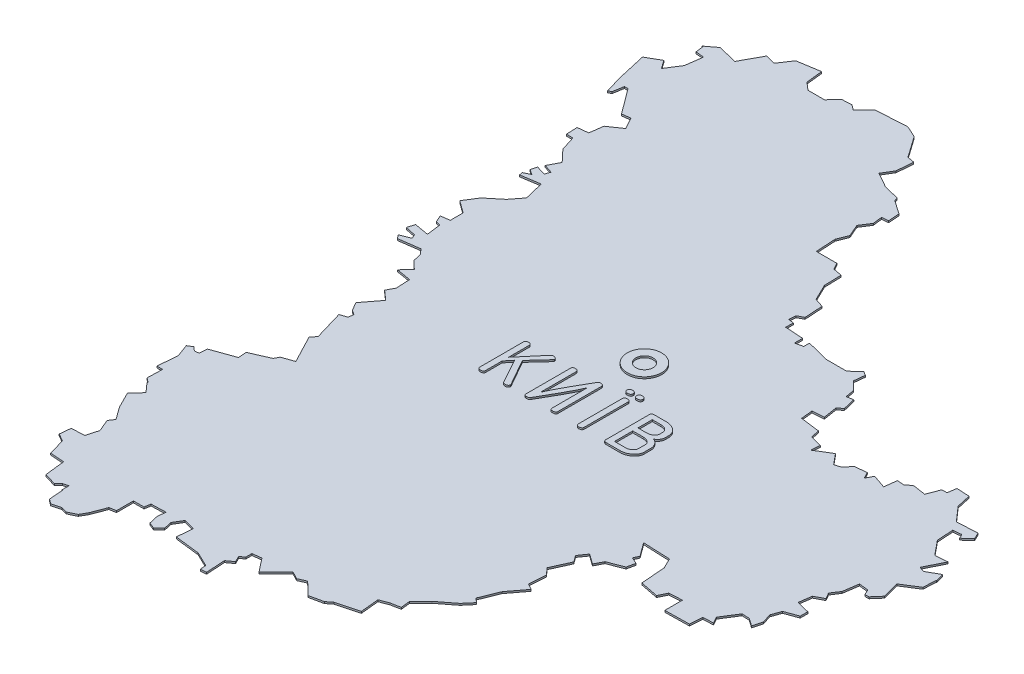
SolidWorks part; units mm, degrees
ref_plane "Спереди" through (0, 0, 0) normal (0, 0, 1) x (1, 0, 0)
ref_plane "Сверху" through (0, 0, 0) normal (0, 1, 0) x (1, 0, 0)
ref_plane "Справа" through (0, 0, 0) normal (1, 0, 0) x (0, 0, -1)
sketch "Эскиз1" plane through (0, 0, 0) normal (0, 1, 0) x (1, 0, 0)
  line B0 (1334.8284, 6150.008) -> (1323.1393, 6150.008)
  line B1 (1323.1393, 6150.008) -> (1316.0248, 6165.596)
  line B2 (1316.0248, 6165.596) -> (1288.7579, 6168.8421)
  line B3 (1288.7579, 6168.8421) -> (1282.253, 6124.7274)
  line B4 (1282.253, 6124.7274) -> (1266.7031, 6100.7193)
  line B5 (1266.7031, 6100.7193) -> (1277.0434, 6083.1806)
  line B6 (1277.0434, 6083.1806) -> (1251.0999, 6069.5408)
  line B7 (1251.0999, 6069.5408) -> (1245.8903, 6032.5584)
  line B8 (1245.8903, 6032.5584) -> (1283.5509, 6023.4805)
  line B9 (1283.5509, 6023.4805) -> (1283.5509, 6001.4155)
  line B10 (1283.5509, 6001.4155) -> (1245.8903, 5987.7858)
  line B11 (1245.8903, 5987.7858) -> (1236.185, 5960.5418)
  line B12 (1236.185, 5960.5418) -> (1244.6457, 5933.2749)
  line B13 (1244.6457, 5933.2749) -> (1237.4804, 5906.0258)
  line B14 (1237.4804, 5906.0258) -> (1215.4484, 5921.5833)
  line B15 (1215.4484, 5921.5833) -> (1193.3403, 5922.8914)
  line B16 (1193.3403, 5922.8914) -> (1164.1455, 5876.8285)
  line B17 (1164.1455, 5876.8285) -> (1174.5366, 5857.9944)
  line B18 (1174.5366, 5857.9944) -> (1145.3139, 5856.7066)
  line B19 (1145.3139, 5856.7066) -> (1142.0881, 5820.3567)
  line B20 (1142.0881, 5820.3567) -> (1072.0299, 5819.0587)
  line B21 (1072.0299, 5819.0587) -> (1072.0299, 5870.3362)
  line B22 (1072.0299, 5870.3362) -> (1034.3972, 5868.3906)
  line B23 (1034.3972, 5868.3906) -> (1022.6573, 5844.3724)
  line B24 (1022.6573, 5844.3724) -> (969.4723, 5854.7432)
  line B25 (969.4723, 5854.7432) -> (964.2881, 5924.8294)
  line B26 (964.2881, 5924.8294) -> (949.3479, 5955.3399)
  line B27 (949.3479, 5955.3399) -> (870.8288, 5958.6038)
  line B28 (870.8288, 5958.6038) -> (899.3886, 5919.6554)
  line B29 (899.3886, 5919.6554) -> (892.8837, 5904.0751)
  line B30 (892.8837, 5904.0751) -> (911.7381, 5895.6423)
  line B31 (911.7381, 5895.6423) -> (906.5285, 5871.6139)
  line B32 (906.5285, 5871.6139) -> (862.4164, 5854.7432)
  line B33 (862.4164, 5854.7432) -> (850.0923, 5830.7427)
  line B34 (850.0923, 5830.7427) -> (820.8696, 5851.5098)
  line B35 (820.8696, 5851.5098) -> (804.0218, 5827.489)
  line B36 (804.0218, 5827.489) -> (817.6184, 5808.693)
  line B37 (817.6184, 5808.693) -> (793.6052, 5755.4597)
  line B38 (793.6052, 5755.4597) -> (811.088, 5735.353)
  line B39 (811.088, 5735.353) -> (807.2755, 5687.3064)
  line B40 (807.2755, 5687.3064) -> (824.7837, 5677.5731)
  line B41 (824.7837, 5677.5731) -> (788.3957, 5629.5722)
  line B42 (788.3957, 5629.5722) -> (766.3383, 5575.0663)
  line B43 (766.3383, 5575.0663) -> (778.6878, 5564.6726)
  line B44 (778.6878, 5564.6726) -> (756.6304, 5538.7291)
  line B45 (756.6304, 5538.7291) -> (710.5879, 5503.0268)
  line B46 (710.5879, 5503.0268) -> (678.1114, 5470.5758)
  line B47 (678.1114, 5470.5758) -> (681.3398, 5443.3368)
  line B48 (681.3398, 5443.3368) -> (654.0983, 5438.1273)
  line B49 (654.0983, 5438.1273) -> (628.1293, 5428.394)
  line B50 (628.1293, 5428.394) -> (633.3388, 5375.209)
  line B51 (633.3388, 5375.209) -> (570.3697, 5358.3129)
  line B52 (570.3697, 5358.3129) -> (554.8198, 5345.9863)
  line B53 (554.8198, 5345.9863) -> (515.8638, 5337.5255)
  line B54 (515.8638, 5337.5255) -> (478.8916, 5373.2532)
  line B55 (478.8916, 5373.2532) -> (456.8088, 5363.4945)
  line B56 (456.8088, 5363.4945) -> (434.0911, 5375.209)
  line B57 (434.0911, 5375.209) -> (384.7948, 5325.8872)
  line B58 (384.7948, 5325.8872) -> (354.3021, 5364.8178)
  line B59 (354.3021, 5364.8178) -> (328.3331, 5361.5387)
  line B60 (328.3331, 5361.5387) -> (328.3331, 5344.6909)
  line B61 (328.3331, 5344.6909) -> (316.644, 5334.2997)
  line B62 (316.644, 5334.2997) -> (325.0794, 5317.4265)
  line B63 (325.0794, 5317.4265) -> (306.2757, 5303.8045)
  line B64 (306.2757, 5303.8045) -> (309.5041, 5248.6382)
  line B65 (309.5041, 5248.6382) -> (292.6309, 5247.3428)
  line B66 (292.6309, 5247.3428) -> (291.3355, 5264.2414)
  line B67 (291.3355, 5264.2414) -> (248.4907, 5285.0009)
  line B68 (248.4907, 5285.0009) -> (176.4767, 5293.4387)
  line B69 (176.4767, 5293.4387) -> (180.3654, 5339.5067)
  line B70 (180.3654, 5339.5067) -> (147.9169, 5347.9446)
  line B71 (147.9169, 5347.9446) -> (132.3391, 5321.9731)
  line B72 (132.3391, 5321.9731) -> (137.5486, 5298.6229)
  line B73 (137.5486, 5298.6229) -> (120.6754, 5283.0197)
  line B74 (120.6754, 5283.0197) -> (103.1418, 5290.185)
  line B75 (103.1418, 5290.185) -> (96.6622, 5318.7219)
  line B76 (96.6622, 5318.7219) -> (99.8906, 5340.7793)
  line B77 (99.8906, 5340.7793) -> (57.0713, 5339.5067)
  line B78 (57.0713, 5339.5067) -> (53.8201, 5321.9731)
  line B79 (53.8201, 5321.9731) -> (23.3274, 5321.9731)
  line B80 (23.3274, 5321.9731) -> (23.3274, 5272.6514)
  line B81 (23.3274, 5272.6514) -> (4.4983, 5269.4002)
  line B82 (4.4983, 5269.4002) -> (-11.0541, 5228.5392)
  line B83 (-11.0541, 5228.5392) -> (-22.7432, 5207.7518)
  line B84 (-22.7432, 5207.7518) -> (-46.7817, 5196.0882)
  line B85 (-46.7817, 5196.0882) -> (-63.6041, 5201.2723)
  line B86 (-63.6041, 5201.2723) -> (-89.5731, 5194.1324)
  line B87 (-89.5731, 5194.1324) -> (-103.218, 5204.526)
  line B88 (-103.218, 5204.526) -> (-106.4717, 5245.387)
  line B89 (-106.4717, 5245.387) -> (-108.4021, 5245.387)
  line B90 (-108.4021, 5245.387) -> (-108.4021, 5266.1464)
  line B91 (-108.4021, 5266.1464) -> (-123.9799, 5262.2577)
  line B92 (-123.9799, 5262.2577) -> (-135.669, 5250.5966)
  line B93 (-135.669, 5250.5966) -> (-170.0759, 5260.9877)
  line B94 (-170.0759, 5260.9877) -> (-174.5971, 5298.6229)
  line B95 (-174.5971, 5298.6229) -> (-176.53, 5318.7219)
  line B96 (-176.53, 5318.7219) -> (-217.4392, 5321.9731)
  line B97 (-217.4392, 5321.9731) -> (-231.0613, 5369.9994)
  line B98 (-231.0613, 5369.9994) -> (-253.1161, 5382.326)
  line B99 (-253.1161, 5382.326) -> (-249.8903, 5414.1141)
  line B100 (-249.8903, 5414.1141) -> (-212.2322, 5416.0699)
  line B101 (-212.2322, 5416.0699) -> (-202.499, 5450.4514)
  line B102 (-202.499, 5450.4514) -> (-217.4392, 5486.1536)
  line B103 (-217.4392, 5486.1536) -> (-207.0481, 5501.7314)
  line B104 (-207.0481, 5501.7314) -> (-232.9917, 5537.4057)
  line B105 (-232.9917, 5537.4057) -> (-257.0048, 5584.7971)
  line B106 (-257.0048, 5584.7971) -> (-231.0613, 5612.699)
  line B107 (-231.0613, 5612.699) -> (-255.7094, 5640.6263)
  line B108 (-255.7094, 5640.6263) -> (-253.1161, 5641.2613)
  line B109 (-253.1161, 5641.2613) -> (-266.7381, 5651.6295)
  line B110 (-266.7381, 5651.6295) -> (-265.4427, 5695.7671)
  line B111 (-265.4427, 5695.7671) -> (-282.3134, 5695.7671)
  line B112 (-282.3134, 5695.7671) -> (-277.1292, 5752.2161)
  line B113 (-277.1292, 5752.2161) -> (-290.7513, 5789.8538)
  line B114 (-290.7513, 5789.8538) -> (-277.1292, 5798.2968)
  line B115 (-277.1292, 5798.2968) -> (-265.4427, 5787.9158)
  line B116 (-265.4427, 5787.9158) -> (-253.1161, 5789.8538)
  line B117 (-253.1161, 5789.8538) -> (-251.8207, 5811.9137)
  line B118 (-251.8207, 5811.9137) -> (-184.9907, 5835.937)
  line B119 (-184.9907, 5835.937) -> (-186.9465, 5859.9502)
  line B120 (-186.9465, 5859.9502) -> (-132.4153, 5883.9532)
  line B121 (-132.4153, 5883.9532) -> (-125.3007, 5897.5777)
  line B122 (-125.3007, 5897.5777) -> (-91.5543, 5909.2643)
  line B123 (-91.5543, 5909.2643) -> (-133.7107, 5989.734)
  line B124 (-133.7107, 5989.734) -> (-122.0241, 6004.6489)
  line B125 (-122.0241, 6004.6489) -> (-147.3327, 6090.3206)
  line B126 (-147.3327, 6090.3206) -> (-127.2311, 6096.8103)
  line B127 (-127.2311, 6096.8103) -> (-125.3007, 6112.3855)
  line B128 (-125.3007, 6112.3855) -> (-137.6248, 6119.5179)
  line B129 (-137.6248, 6119.5179) -> (-152.5168, 6144.8239)
  line B130 (-152.5168, 6144.8239) -> (-114.9071, 6194.1481)
  line B131 (-114.9071, 6194.1481) -> (-142.1486, 6218.1588)
  line B132 (-142.1486, 6218.1588) -> (-130.4849, 6240.2212)
  line B133 (-130.4849, 6240.2212) -> (-132.4153, 6281.1101)
  line B134 (-132.4153, 6281.1101) -> (-174.5971, 6288.2501)
  line B135 (-174.5971, 6288.2501) -> (-151.2443, 6313.5459)
  line B136 (-151.2443, 6313.5459) -> (-174.5971, 6336.2637)
  line B137 (-174.5971, 6336.2637) -> (-179.7812, 6359.6368)
  line B138 (-179.7812, 6359.6368) -> (-193.4261, 6375.207)
  line B139 (-193.4261, 6375.207) -> (-253.1161, 6366.7691)
  line B140 (-253.1161, 6366.7691) -> (-262.2144, 6377.1602)
  line B141 (-262.2144, 6377.1602) -> (-232.9917, 6388.8239)
  line B142 (-232.9917, 6388.8239) -> (-238.2012, 6401.1658)
  line B143 (-238.2012, 6401.1658) -> (-268.6939, 6407.6326)
  line B144 (-268.6939, 6407.6326) -> (-262.2144, 6428.3946)
  line B145 (-262.2144, 6428.3946) -> (-220.6676, 6421.2851)
  line B146 (-220.6676, 6421.2851) -> (-225.8517, 6462.1512)
  line B147 (-225.8517, 6462.1512) -> (-239.4966, 6466.0551)
  line B148 (-239.4966, 6466.0551) -> (-248.5695, 6486.1719)
  line B149 (-248.5695, 6486.1719) -> (-222.6234, 6489.4333)
  line B150 (-222.6234, 6489.4333) -> (-222.6234, 6527.0431)
  line B151 (-222.6234, 6527.0431) -> (-258.3002, 6553.012)
  line B152 (-258.3002, 6553.012) -> (-234.3125, 6590.6472)
  line B153 (-234.3125, 6590.6472) -> (-193.4261, 6624.3937)
  line B154 (-193.4261, 6624.3937) -> (-168.1175, 6656.8396)
  line B155 (-168.1175, 6656.8396) -> (-181.7395, 6713.2962)
  line B156 (-181.7395, 6713.2962) -> (-236.2454, 6704.8532)
  line B157 (-236.2454, 6704.8532) -> (-238.2012, 6714.5992)
  line B158 (-238.2012, 6714.5992) -> (-219.3722, 6723.6772)
  line B159 (-219.3722, 6723.6772) -> (-234.3125, 6733.4105)
  line B160 (-234.3125, 6733.4105) -> (-229.7659, 6750.9263)
  line B161 (-229.7659, 6750.9263) -> (-202.499, 6742.496)
  line B162 (-202.499, 6742.496) -> (-197.3148, 6757.4262)
  line B163 (-197.3148, 6757.4262) -> (-222.6234, 6765.8691)
  line B164 (-222.6234, 6765.8691) -> (-205.7527, 6798.2821)
  line B165 (-205.7527, 6798.2821) -> (-238.2012, 6832.7067)
  line B166 (-238.2012, 6832.7067) -> (-251.8207, 6875.5311)
  line B167 (-251.8207, 6875.5311) -> (-270.6243, 6875.5311)
  line B168 (-270.6243, 6875.5311) -> (-271.9476, 6907.9643)
  line B169 (-271.9476, 6907.9643) -> (-241.427, 6911.2232)
  line B170 (-241.427, 6911.2232) -> (-236.2454, 6950.1868)
  line B171 (-236.2454, 6950.1868) -> (-198.6102, 6976.1049)
  line B172 (-198.6102, 6976.1049) -> (-217.4392, 7009.8768)
  line B173 (-217.4392, 7009.8768) -> (-241.427, 7006.6256)
  line B174 (-241.427, 7006.6256) -> (-295.9354, 7079.9427)
  line B175 (-295.9354, 7079.9427) -> (-306.3265, 7079.9427)
  line B176 (-306.3265, 7079.9427) -> (-311.5107, 7049.4474)
  line B177 (-311.5107, 7049.4474) -> (-319.9486, 7044.2658)
  line B178 (-319.9486, 7044.2658) -> (-335.5238, 7097.456)
  line B179 (-335.5238, 7097.456) -> (-354.3529, 7180.5267)
  line B180 (-354.3529, 7180.5267) -> (-314.7644, 7203.247)
  line B181 (-314.7644, 7203.247) -> (-297.8912, 7179.2389)
  line B182 (-297.8912, 7179.2389) -> (-271.9476, 7220.0999)
  line B183 (-271.9476, 7220.0999) -> (-265.4427, 7269.4267)
  line B184 (-265.4427, 7269.4267) -> (-289.4559, 7271.3901)
  line B185 (-289.4559, 7271.3901) -> (-292.7071, 7295.3956)
  line B186 (-292.7071, 7295.3956) -> (-295.3004, 7294.7327)
  line B187 (-295.3004, 7294.7327) -> (-294.6375, 7295.3956)
  line B188 (-294.6375, 7295.3956) -> (-265.4427, 7317.4606)
  line B189 (-265.4427, 7317.4606) -> (-209.0039, 7303.8386)
  line B190 (-209.0039, 7303.8386) -> (-176.53, 7363.5083)
  line B191 (-176.53, 7363.5083) -> (-147.3327, 7356.3861)
  line B192 (-147.3327, 7356.3861) -> (-122.0241, 7394.0162)
  line B193 (-122.0241, 7394.0162) -> (-57.15, 7404.4175)
  line B194 (-57.15, 7404.4175) -> (-51.9405, 7356.3861)
  line B195 (-51.9405, 7356.3861) -> (-29.8831, 7337.5723)
  line B196 (-29.8831, 7337.5723) -> (18.1178, 7337.5723)
  line B197 (18.1178, 7337.5723) -> (42.131, 7363.5083)
  line B198 (42.131, 7363.5083) -> (70.6933, 7364.8265)
  line B199 (70.6933, 7364.8265) -> (86.294, 7353.1476)
  line B200 (86.294, 7353.1476) -> (118.7196, 7385.5859)
  line B201 (118.7196, 7385.5859) -> (207.6069, 7390.7828)
  line B202 (207.6069, 7390.7828) -> (241.3508, 7375.2075)
  line B203 (241.3508, 7375.2075) -> (284.193, 7314.2094)
  line B204 (284.193, 7314.2094) -> (304.9549, 7310.3232)
  line B205 (304.9549, 7310.3232) -> (301.0662, 7262.9446)
  line B206 (301.0662, 7262.9446) -> (282.2626, 7231.7864)
  line B207 (282.2626, 7231.7864) -> (327.0377, 7206.488)
  line B208 (327.0377, 7206.488) -> (371.1499, 7196.0969)
  line B209 (371.1499, 7196.0969) -> (374.4011, 7185.7184)
  line B210 (374.4011, 7185.7184) -> (413.9921, 7158.4668)
  line B211 (413.9921, 7158.4668) -> (415.9225, 7126.0233)
  line B212 (415.9225, 7126.0233) -> (397.1188, 7124.733)
  line B213 (397.1188, 7124.733) -> (400.3726, 7097.456)
  line B214 (400.3726, 7097.456) -> (381.5436, 7068.2612)
  line B215 (381.5436, 7068.2612) -> (397.1188, 7032.5767)
  line B216 (397.1188, 7032.5767) -> (384.7948, 7001.416)
  line B217 (384.7948, 7001.416) -> (388.0231, 6943.6717)
  line B218 (388.0231, 6943.6717) -> (447.7131, 6943.6717)
  line B219 (447.7131, 6943.6717) -> (458.1042, 6924.863)
  line B220 (458.1042, 6924.863) -> (484.0757, 6919.6636)
  line B221 (484.0757, 6919.6636) -> (485.3711, 6870.3241)
  line B222 (485.3711, 6870.3241) -> (508.7239, 6822.3105)
  line B223 (508.7239, 6822.3105) -> (534.6929, 6813.87)
  line B224 (534.6929, 6813.87) -> (537.9212, 6761.3022)
  line B225 (537.9212, 6761.3022) -> (521.0734, 6752.2344)
  line B226 (521.0734, 6752.2344) -> (519.1176, 6732.1049)
  line B227 (519.1176, 6732.1049) -> (534.6929, 6730.1618)
  line B228 (534.6929, 6730.1618) -> (534.6929, 6708.0968)
  line B229 (534.6929, 6708.0968) -> (587.2429, 6704.8532)
  line B230 (587.2429, 6704.8532) -> (587.2429, 6680.8502)
  line B231 (587.2429, 6680.8502) -> (609.3257, 6686.0395)
  line B232 (609.3257, 6686.0395) -> (609.3257, 6702.9051)
  line B233 (609.3257, 6702.9051) -> (672.9019, 6686.0395)
  line B234 (672.9019, 6686.0395) -> (733.8898, 6686.0395)
  line B235 (733.8898, 6686.0395) -> (759.8588, 6710.0653)
  line B236 (759.8588, 6710.0653) -> (771.5479, 6702.9051)
  line B237 (771.5479, 6702.9051) -> (768.2941, 6672.3997)
  line B238 (768.2941, 6672.3997) -> (792.3073, 6648.4017)
  line B239 (792.3073, 6648.4017) -> (797.5168, 6621.1552)
  line B240 (797.5168, 6621.1552) -> (816.3458, 6624.3937)
  line B241 (816.3458, 6624.3937) -> (824.7837, 6588.7143)
  line B242 (824.7837, 6588.7143) -> (811.088, 6578.3206)
  line B243 (811.088, 6578.3206) -> (817.6184, 6537.4393)
  line B244 (817.6184, 6537.4393) -> (783.8719, 6535.481)
  line B245 (783.8719, 6535.481) -> (787.1257, 6501.7447)
  line B246 (787.1257, 6501.7447) -> (843.5873, 6494.6098)
  line B247 (843.5873, 6494.6098) -> (848.7715, 6469.2962)
  line B248 (848.7715, 6469.2962) -> (882.49, 6460.8532)
  line B249 (882.49, 6460.8532) -> (880.5596, 6434.9046)
  line B250 (880.5596, 6434.9046) -> (925.3347, 6462.1512)
  line B251 (925.3347, 6462.1512) -> (950.6433, 6431.6534)
  line B252 (950.6433, 6431.6534) -> (968.1769, 6436.8451)
  line B253 (968.1769, 6436.8451) -> (985.0755, 6456.9696)
  line B254 (985.0755, 6456.9696) -> (1019.429, 6460.8532)
  line B255 (1019.429, 6460.8532) -> (1029.1623, 6442.0572)
  line B256 (1029.1623, 6442.0572) -> (1039.556, 6462.1512)
  line B257 (1039.556, 6462.1512) -> (1079.1698, 6448.5495)
  line B258 (1079.1698, 6448.5495) -> (1083.6681, 6484.2314)
  line B259 (1083.6681, 6484.2314) -> (1104.4555, 6482.9258)
  line B260 (1104.4555, 6482.9258) -> (1118.1004, 6494.6098)
  line B261 (1118.1004, 6494.6098) -> (1125.2403, 6494.6098)
  line B262 (1125.2403, 6494.6098) -> (1157.6634, 6489.4333)
  line B263 (1157.6634, 6489.4333) -> (1171.2854, 6525.7604)
  line B264 (1171.2854, 6525.7604) -> (1186.2003, 6525.7604)
  line B265 (1186.2003, 6525.7604) -> (1190.0891, 6551.0461)
  line B266 (1190.0891, 6551.0461) -> (1227.1121, 6549.1157)
  line B267 (1227.1121, 6549.1157) -> (1236.185, 6508.2293)
  line B268 (1236.185, 6508.2293) -> (1273.1572, 6466.0551)
  line B269 (1273.1572, 6466.0551) -> (1332.898, 6469.2962)
  line B270 (1332.898, 6469.2962) -> (1341.9684, 6450.4773)
  line B271 (1341.9684, 6450.4773) -> (1319.2531, 6429.7179)
  line B272 (1319.2531, 6429.7179) -> (1312.7711, 6442.0572)
  line B273 (1312.7711, 6442.0572) -> (1288.7579, 6440.0862)
  line B274 (1288.7579, 6440.0862) -> (1292.0116, 6392.0675)
  line B275 (1292.0116, 6392.0675) -> (1326.3931, 6349.8984)
  line B276 (1326.3931, 6349.8984) -> (1362.0699, 6353.1394)
  line B277 (1362.0699, 6353.1394) -> (1334.8284, 6298.626)
  line B278 (1334.8284, 6298.626) -> (1350.4062, 6293.452)
  line B279 (1350.4062, 6293.452) -> (1386.0577, 6313.5459)
  line B280 (1386.0577, 6313.5459) -> (1392.6134, 6290.1881)
  line B281 (1392.6134, 6290.1881) -> (1391.2672, 6290.1881)
  line B282 (1391.2672, 6290.1881) -> (1389.3597, 6252.5504)
  line B283 (1389.3597, 6252.5504) -> (1343.2409, 6223.3454)
  line B284 (1343.2409, 6223.3454) -> (1356.2254, 6174.6663)
  line B285 (1356.2254, 6174.6663) -> (1334.8284, 6150.008)
sketch_block_instance "Блок19-1"
sketch_block "Блок19"
extrude "Бобышка-Вытянуть1" add sketch "Эскиз1" along normal blind 5 contours B285 B284 B283 B282 B281 B280 B279 B278 B277 B276 B275 B274 B273 B272 B271 B270 B269 B268 B267 B266 B265 B264 B263 B262 B261 B260 B259 B258 B257 B256 B255 B254 B253 B252 B251 B250 B249 B248 B247 B246 B245 B244 B243 B242 B241 B240 B239 B238 B237 B236 B235 region at (351.1866, 0, -6249.637)
sketch "Эскиз2" plane through (0, 0, 0) normal (0, 1, 0) x (1, 0, 0)
  line L0 (181.8307, 6151.3374) -> (2228.0138, 6151.3374) construction
  circle A0 centre (423.7713, 6408.0672) radius 25
  circle A1 centre (423.7713, 6408.0672) radius 50
  text T0 "<b>КИЇВ</b>" font "GOST Type AU" height 140
  dimension "D1" = 50
  dimension "D2" = 100
extrude "Бобышка-Вытянуть2" add sketch "Эскиз2" along normal blind 10
scale "Масштаб1" scale about centroid uniform scaling yes scale factor 0.05
